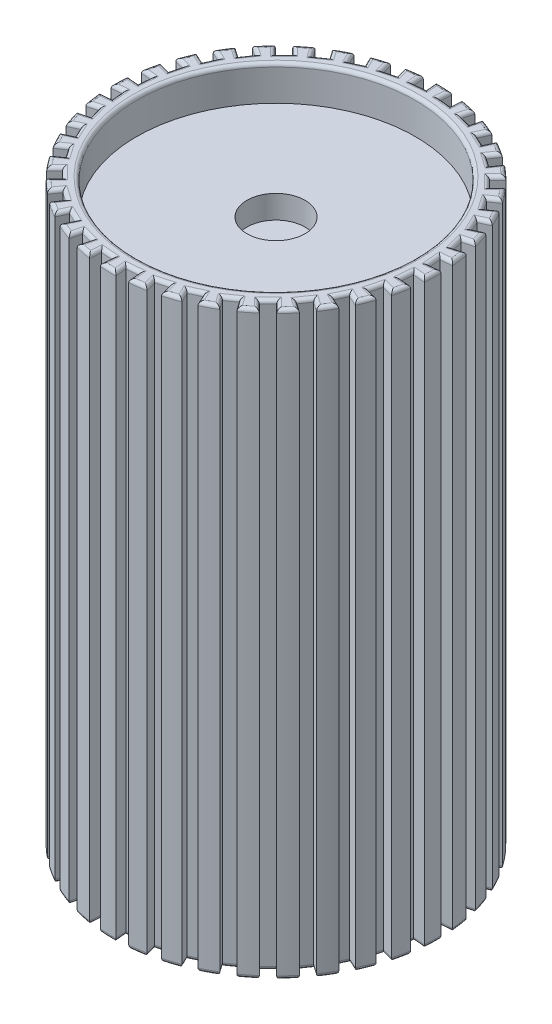
SolidWorks part; units mm, degrees
ref_plane "Front Plane" through (0, 0, 0) normal (0, 0, 1) x (1, 0, 0)
ref_plane "Top Plane" through (0, 0, 0) normal (0, 1, 0) x (1, 0, 0)
ref_plane "Right Plane" through (0, 0, 0) normal (1, 0, 0) x (0, 0, -1)
other "Configuration Table"
sketch "草图1" plane through (0, 0, 0) normal (0, 1, 0) x (1, 0, 0)
  circle A0 centre (0, 0) radius 13
  dimension "D1" = 26
extrude "凸台-拉伸1" add sketch "草图1" along normal blind 50
sketch "草图6" plane through (0, 50, 0) normal (0, 1, 0) x (1, 0, 0)
  circle A0 centre (0, 0) radius 14
  dimension "D1" = 28
extrude "凸台-拉伸4" add sketch "草图6" against normal through all
sketch "草图2" plane through (0, 50, 0) normal (0, 1, 0) x (1, 0, 0)
  circle A0 centre (0, 0) radius 12
  dimension "D1" = 24
extrude "切除-拉伸1" cut sketch "草图2" against normal blind 3
sketch "草图7" plane through (0, 50, 0) normal (0, 1, 0) x (1, 0, 0)
  line L0 (-15.6468, 4.1422) -> (-12.5671, 3.3269)
  line L1 (-15.6468, 4.1422) -> (-15.3762, 5.1646)
  line L2 (-12.5671, 3.3269) -> (-12.2964, 4.3493)
  line L3 (-15.3762, 5.1646) -> (-12.2964, 4.3493)
  line L4 (-14.6898, 6.7963) -> (-11.7985, 5.4586)
  line L5 (-14.6898, 6.7963) -> (-14.2457, 7.7562)
  line L6 (-14.2457, 7.7562) -> (-11.3544, 6.4185)
  line L7 (-11.7985, 5.4586) -> (-11.3544, 6.4185)
  line L8 (-13.2865, 9.2439) -> (-10.6713, 7.4245)
  line L9 (-13.2865, 9.2439) -> (-12.6825, 10.1121)
  line L10 (-12.6825, 10.1121) -> (-10.0673, 8.2926)
  line L11 (-10.6713, 7.4245) -> (-10.0673, 8.2926)
  line L12 (-11.4794, 11.4107) -> (-9.22, 9.1647)
  line L13 (-11.4794, 11.4107) -> (-10.7338, 12.1608)
  line L14 (-10.7338, 12.1608) -> (-8.4744, 9.9148)
  line L15 (-9.22, 9.1647) -> (-8.4744, 9.9148)
  line L16 (-9.3236, 13.2307) -> (-7.4884, 10.6265)
  line L17 (-9.3236, 13.2307) -> (-8.4591, 13.8399)
  line L18 (-8.4591, 13.8399) -> (-6.6239, 11.2358)
  line L19 (-7.4884, 10.6265) -> (-6.6239, 11.2358)
  line L20 (-6.8845, 14.6487) -> (-5.5294, 11.7654)
  line L21 (-6.8845, 14.6487) -> (-5.9273, 15.0986)
  line L22 (-5.9273, 15.0986) -> (-4.5722, 12.2153)
  line L23 (-5.5294, 11.7654) -> (-4.5722, 12.2153)
  line L24 (-4.2361, 15.6217) -> (-3.4024, 12.5469)
  line L25 (-4.2361, 15.6217) -> (-3.2154, 15.8985)
  line L26 (-3.2154, 15.8985) -> (-2.3816, 12.8237)
  line L27 (-3.4024, 12.5469) -> (-2.3816, 12.8237)
  line L28 (-1.4591, 16.1199) -> (-1.1719, 12.9471)
  line L29 (-1.4591, 16.1199) -> (-0.4058, 16.2153)
  line L30 (-0.4058, 16.2153) -> (-0.1186, 13.0424)
  line L31 (-1.1719, 12.9471) -> (-0.1186, 13.0424)
  line L32 (1.3622, 16.1284) -> (1.0941, 12.9539)
  line L33 (1.3622, 16.1284) -> (2.4161, 16.0394)
  line L34 (2.4161, 16.0394) -> (2.148, 12.8649)
  line L35 (1.0941, 12.9539) -> (2.148, 12.8649)
  line L36 (4.1422, 15.6468) -> (3.3269, 12.5671)
  line L37 (4.1422, 15.6468) -> (5.1646, 15.3762)
  line L38 (5.1646, 15.3762) -> (4.3493, 12.2964)
  line L39 (3.3269, 12.5671) -> (4.3493, 12.2964)
  line L40 (6.7963, 14.6898) -> (5.4586, 11.7985)
  line L41 (6.7963, 14.6898) -> (7.7562, 14.2457)
  line L42 (7.7562, 14.2457) -> (6.4185, 11.3544)
  line L43 (5.4586, 11.7985) -> (6.4185, 11.3544)
  line L44 (9.2439, 13.2865) -> (7.4245, 10.6713)
  line L45 (9.2439, 13.2865) -> (10.1121, 12.6825)
  line L46 (10.1121, 12.6825) -> (8.2926, 10.0673)
  line L47 (7.4245, 10.6713) -> (8.2926, 10.0673)
  line L48 (11.4107, 11.4794) -> (9.1647, 9.22)
  line L49 (11.4107, 11.4794) -> (12.1608, 10.7338)
  line L50 (12.1608, 10.7338) -> (9.9148, 8.4744)
  line L51 (9.1647, 9.22) -> (9.9148, 8.4744)
  line L52 (13.2307, 9.3236) -> (10.6265, 7.4884)
  line L53 (13.2307, 9.3236) -> (13.8399, 8.4591)
  line L54 (13.8399, 8.4591) -> (11.2358, 6.6239)
  line L55 (10.6265, 7.4884) -> (11.2358, 6.6239)
  line L56 (14.6487, 6.8845) -> (11.7654, 5.5294)
  line L57 (14.6487, 6.8845) -> (15.0986, 5.9273)
  line L58 (15.0986, 5.9273) -> (12.2153, 4.5722)
  line L59 (11.7654, 5.5294) -> (12.2153, 4.5722)
  line L60 (15.6217, 4.2361) -> (12.5469, 3.4024)
  line L61 (15.6217, 4.2361) -> (15.8985, 3.2154)
  line L62 (15.8985, 3.2154) -> (12.8237, 2.3816)
  line L63 (12.5469, 3.4024) -> (12.8237, 2.3816)
  line L64 (16.1199, 1.4591) -> (12.9471, 1.1719)
  line L65 (16.1199, 1.4591) -> (16.2153, 0.4058)
  line L66 (16.2153, 0.4058) -> (13.0424, 0.1186)
  line L67 (12.9471, 1.1719) -> (13.0424, 0.1186)
  line L68 (16.1284, -1.3622) -> (12.9539, -1.0941)
  line L69 (16.1284, -1.3622) -> (16.0394, -2.4161)
  line L70 (16.0394, -2.4161) -> (12.8649, -2.148)
  line L71 (12.9539, -1.0941) -> (12.8649, -2.148)
  line L72 (15.6468, -4.1422) -> (12.5671, -3.3269)
  line L73 (15.6468, -4.1422) -> (15.3762, -5.1646)
  line L74 (15.3762, -5.1646) -> (12.2964, -4.3493)
  line L75 (12.5671, -3.3269) -> (12.2964, -4.3493)
  line L76 (14.6898, -6.7963) -> (11.7985, -5.4586)
  line L77 (14.6898, -6.7963) -> (14.2457, -7.7562)
  line L78 (14.2457, -7.7562) -> (11.3544, -6.4185)
  line L79 (11.7985, -5.4586) -> (11.3544, -6.4185)
  line L80 (13.2865, -9.2439) -> (10.6713, -7.4245)
  line L81 (13.2865, -9.2439) -> (12.6825, -10.1121)
  line L82 (12.6825, -10.1121) -> (10.0673, -8.2926)
  line L83 (10.6713, -7.4245) -> (10.0673, -8.2926)
  line L84 (11.4794, -11.4107) -> (9.22, -9.1647)
  line L85 (11.4794, -11.4107) -> (10.7338, -12.1608)
  line L86 (10.7338, -12.1608) -> (8.4744, -9.9148)
  line L87 (9.22, -9.1647) -> (8.4744, -9.9148)
  line L88 (9.3236, -13.2307) -> (7.4884, -10.6265)
  line L89 (9.3236, -13.2307) -> (8.4591, -13.8399)
  line L90 (8.4591, -13.8399) -> (6.6239, -11.2358)
  line L91 (7.4884, -10.6265) -> (6.6239, -11.2358)
  line L92 (6.8845, -14.6487) -> (5.5294, -11.7654)
  line L93 (6.8845, -14.6487) -> (5.9273, -15.0986)
  line L94 (5.9273, -15.0986) -> (4.5722, -12.2153)
  line L95 (5.5294, -11.7654) -> (4.5722, -12.2153)
  line L96 (4.2361, -15.6217) -> (3.4024, -12.5469)
  line L97 (4.2361, -15.6217) -> (3.2154, -15.8985)
  line L98 (3.2154, -15.8985) -> (2.3816, -12.8237)
  line L99 (3.4024, -12.5469) -> (2.3816, -12.8237)
  line L100 (1.4591, -16.1199) -> (1.1719, -12.9471)
  line L101 (1.4591, -16.1199) -> (0.4058, -16.2153)
  line L102 (0.4058, -16.2153) -> (0.1186, -13.0424)
  line L103 (1.1719, -12.9471) -> (0.1186, -13.0424)
  line L104 (-1.3622, -16.1284) -> (-1.0941, -12.9539)
  line L105 (-1.3622, -16.1284) -> (-2.4161, -16.0394)
  line L106 (-2.4161, -16.0394) -> (-2.148, -12.8649)
  line L107 (-1.0941, -12.9539) -> (-2.148, -12.8649)
  line L108 (-4.1422, -15.6468) -> (-3.3269, -12.5671)
  line L109 (-4.1422, -15.6468) -> (-5.1646, -15.3762)
  line L110 (-5.1646, -15.3762) -> (-4.3493, -12.2964)
  line L111 (-3.3269, -12.5671) -> (-4.3493, -12.2964)
  line L112 (-6.7963, -14.6898) -> (-5.4586, -11.7985)
  line L113 (-6.7963, -14.6898) -> (-7.7562, -14.2457)
  line L114 (-7.7562, -14.2457) -> (-6.4185, -11.3544)
  line L115 (-5.4586, -11.7985) -> (-6.4185, -11.3544)
  line L116 (-9.2439, -13.2865) -> (-7.4245, -10.6713)
  line L117 (-9.2439, -13.2865) -> (-10.1121, -12.6825)
  line L118 (-10.1121, -12.6825) -> (-8.2926, -10.0673)
  line L119 (-7.4245, -10.6713) -> (-8.2926, -10.0673)
  line L120 (-11.4107, -11.4794) -> (-9.1647, -9.22)
  line L121 (-11.4107, -11.4794) -> (-12.1608, -10.7338)
  line L122 (-12.1608, -10.7338) -> (-9.9148, -8.4744)
  line L123 (-9.1647, -9.22) -> (-9.9148, -8.4744)
  line L124 (-13.2307, -9.3236) -> (-10.6265, -7.4884)
  line L125 (-13.2307, -9.3236) -> (-13.8399, -8.4591)
  line L126 (-13.8399, -8.4591) -> (-11.2358, -6.6239)
  line L127 (-10.6265, -7.4884) -> (-11.2358, -6.6239)
  line L128 (-14.6487, -6.8845) -> (-11.7654, -5.5294)
  line L129 (-14.6487, -6.8845) -> (-15.0986, -5.9273)
  line L130 (-15.0986, -5.9273) -> (-12.2153, -4.5722)
  line L131 (-11.7654, -5.5294) -> (-12.2153, -4.5722)
  line L132 (-15.6217, -4.2361) -> (-12.5469, -3.4024)
  line L133 (-15.6217, -4.2361) -> (-15.8985, -3.2154)
  line L134 (-15.8985, -3.2154) -> (-12.8237, -2.3816)
  line L135 (-12.5469, -3.4024) -> (-12.8237, -2.3816)
  line L136 (-16.1199, -1.4591) -> (-12.9471, -1.1719)
  line L137 (-16.1199, -1.4591) -> (-16.2153, -0.4058)
  line L138 (-16.2153, -0.4058) -> (-13.0424, -0.1186)
  line L139 (-12.9471, -1.1719) -> (-13.0424, -0.1186)
  line L140 (-16.1284, 1.3622) -> (-12.9539, 1.0941)
  line L141 (-16.1284, 1.3622) -> (-16.0394, 2.4161)
  line L142 (-16.0394, 2.4161) -> (-12.8649, 2.148)
  line L143 (-12.9539, 1.0941) -> (-12.8649, 2.148)
  circle A0 centre (0, 0) radius 13 construction
  point P150 (0, 0)
  dimension "D1" = 26
  dimension "D2" = 36
extrude "切除-拉伸2" cut sketch "草图7" against normal through all
sketch "草图8" plane through (0, 47, 0) normal (0, 1, 0) x (1, 0, 0)
  circle A0 centre (0, 0) radius 2.5
  dimension "D1" = 5
extrude "切除-拉伸3" cut sketch "草图8" against normal blind 2
fillet "圆角6" radius 0.3 144 edges at (1.1362, 0, -13.4521) (0.4872, 0, -13.9915) (-0.1619, 0, -13.5205) (-0.6453, 0, -12.9947) (-1.217, 0, -13.445) (-1.9498, 0, -13.8636) (-2.5072, 0, -13.2869) (-2.892, 0, -12.6853) (-3.5332, 0, -13.0294) (-4.3276, 0, -13.3143) (-4.7764, 0, -12.6497) (-5.0508, 0, -11.9904) (-5.7421, 0, -12.218) (-6.5739, 0, -12.3606) (-6.9004, 0, -11.6281) (-7.0562, 0, -10.9311) (-7.7765, 0, -11.0352) (-8.6204, 0, -11.0313) (-8.8148, 0, -10.2532) (-8.8472, 0, -9.5398) (-9.5746, 0, -9.5172) (-10.405, 0, -9.3668) (-10.4613, 0, -8.5668) (-10.3693, 0, -7.8586) (-11.0818, 0, -7.71) (-11.8734, 0, -7.4177) (-11.79, 0, -6.62) (-11.5764, 0, -5.9386) (-12.2522, 0, -5.6686) (-12.9811, 0, -5.2432) (-12.7604, 0, -4.4722) (-12.4318, 0, -3.8381) (-13.0504, 0, -3.4549) (-13.6944, 0, -2.9094) (-13.3432, 0, -2.1884) (-12.9094, 0, -1.6211) (-13.4521, 0, -1.1362) (-13.9915, 0, -0.4872) (-13.5205, 0, 0.1619) (-12.9947, 0, 0.6453) (-13.445, 0, 1.217) (-13.8636, 0, 1.9498) (-13.2869, 0, 2.5072) (-12.6853, 0, 2.892) (-13.0294, 0, 3.5332) (-13.3143, 0, 4.3276) (-12.6497, 0, 4.7764) (-11.9904, 0, 5.0508) (-12.218, 0, 5.7421) (-12.3606, 0, 6.5739) (-11.6281, 0, 6.9004) (-10.9311, 0, 7.0562) (-11.0352, 0, 7.7765) (-11.0313, 0, 8.6204) (-10.2532, 0, 8.8148) (-9.5398, 0, 8.8472) (-9.5172, 0, 9.5746) (-9.3668, 0, 10.405) (-8.5668, 0, 10.4613) (-7.8586, 0, 10.3693) (-7.71, 0, 11.0818) (-7.4177, 0, 11.8734) (-6.62, 0, 11.79) (-5.9386, 0, 11.5764) (-5.6686, 0, 12.2522) (-5.2432, 0, 12.9811) (-4.4722, 0, 12.7604) (-3.8381, 0, 12.4318) (-3.4549, 0, 13.0504) (-2.9094, 0, 13.6944) (-2.1884, 0, 13.3432) (-1.6211, 0, 12.9094) (-1.1362, 0, 13.4521) (-0.4872, 0, 13.9915) (0.1619, 0, 13.5205) (0.6453, 0, 12.9947) (1.217, 0, 13.445) (1.9498, 0, 13.8636) (2.5072, 0, 13.2869) (2.892, 0, 12.6853) (3.5332, 0, 13.0294) (4.3276, 0, 13.3143) (4.7764, 0, 12.6497) (5.0508, 0, 11.9904) (5.7421, 0, 12.218) (6.5739, 0, 12.3606) (6.9004, 0, 11.6281) (7.0562, 0, 10.9311) (7.7765, 0, 11.0352) (8.6204, 0, 11.0313) (8.8148, 0, 10.2532) (8.8472, 0, 9.5398) (9.5746, 0, 9.5172) (10.405, 0, 9.3668) (10.4613, 0, 8.5668) (10.3693, 0, 7.8586) (11.0818, 0, 7.71) (11.8734, 0, 7.4177) (11.79, 0, 6.62) (11.5764, 0, 5.9386) (12.2522, 0, 5.6686) (12.9811, 0, 5.2432) (12.7604, 0, 4.4722) (12.4318, 0, 3.8381) (13.0504, 0, 3.4549) (13.6944, 0, 2.9094) (13.3432, 0, 2.1884) (12.9094, 0, 1.6211) (13.4521, 0, 1.1362) (13.9915, 0, 0.4872) (13.5205, 0, -0.1619) (12.9947, 0, -0.6453) (13.445, 0, -1.217) (13.8636, 0, -1.9498) (13.2869, 0, -2.5072) (12.6853, 0, -2.892) (13.0294, 0, -3.5332) (13.3143, 0, -4.3276) (12.6497, 0, -4.7764) (11.9904, 0, -5.0508) (12.218, 0, -5.7421) (12.3606, 0, -6.5739) (11.6281, 0, -6.9004) (10.9311, 0, -7.0562) (11.0352, 0, -7.7765) (11.0313, 0, -8.6204) (10.2532, 0, -8.8148) (9.5398, 0, -8.8472) (9.5172, 0, -9.5746) (9.3668, 0, -10.405) (8.5668, 0, -10.4613) (7.8586, 0, -10.3693) (7.71, 0, -11.0818) (7.4177, 0, -11.8734) (6.62, 0, -11.79) (5.9386, 0, -11.5764) (5.6686, 0, -12.2522) (5.2432, 0, -12.9811) (4.4722, 0, -12.7604) (3.8381, 0, -12.4318) (3.4549, 0, -13.0504) (2.9094, 0, -13.6944) (2.1884, 0, -13.3432) (1.6211, 0, -12.9094)
fillet "圆角7" radius 0.3 145 edges at (0, 50, 12) (2.9094, 50, -13.6944) (3.4549, 50, -13.0504) (3.8381, 50, -12.4318) (4.4722, 50, -12.7604) (5.2432, 50, -12.9811) (5.6686, 50, -12.2522) (5.9386, 50, -11.5764) (6.62, 50, -11.79) (7.4177, 50, -11.8734) (7.71, 50, -11.0818) (7.8586, 50, -10.3693) (8.5668, 50, -10.4613) (9.3668, 50, -10.405) (9.5172, 50, -9.5746) (9.5398, 50, -8.8472) (10.2532, 50, -8.8148) (11.0313, 50, -8.6204) (11.0352, 50, -7.7765) (10.9311, 50, -7.0562) (11.6281, 50, -6.9004) (12.3606, 50, -6.5739) (12.218, 50, -5.7421) (11.9904, 50, -5.0508) (12.6497, 50, -4.7764) (13.3143, 50, -4.3276) (13.0294, 50, -3.5332) (12.6853, 50, -2.892) (13.2869, 50, -2.5072) (13.8636, 50, -1.9498) (13.445, 50, -1.217) (12.9947, 50, -0.6453) (13.5205, 50, -0.1619) (13.9915, 50, 0.4872) (13.4521, 50, 1.1362) (12.9094, 50, 1.6211) (13.3432, 50, 2.1884) (13.6944, 50, 2.9094) (13.0504, 50, 3.4549) (12.4318, 50, 3.8381) (12.7604, 50, 4.4722) (12.9811, 50, 5.2432) (12.2522, 50, 5.6686) (11.5764, 50, 5.9386) (11.79, 50, 6.62) (11.8734, 50, 7.4177) (11.0818, 50, 7.71) (10.3693, 50, 7.8586) (10.4613, 50, 8.5668) (10.405, 50, 9.3668) (9.5746, 50, 9.5172) (8.8472, 50, 9.5398) (8.8148, 50, 10.2532) (8.6204, 50, 11.0313) (7.7765, 50, 11.0352) (7.0562, 50, 10.9311) (6.9004, 50, 11.6281) (6.5739, 50, 12.3606) (5.7421, 50, 12.218) (5.0508, 50, 11.9904) (4.7764, 50, 12.6497) (4.3276, 50, 13.3143) (3.5332, 50, 13.0294) (2.892, 50, 12.6853) (2.5072, 50, 13.2869) (1.9498, 50, 13.8636) (1.217, 50, 13.445) (0.6453, 50, 12.9947) (0.1619, 50, 13.5205) (-0.4872, 50, 13.9915) (-1.1362, 50, 13.4521) (-1.6211, 50, 12.9094) (-2.1884, 50, 13.3432) (-2.9094, 50, 13.6944) (-3.4549, 50, 13.0504) (-3.8381, 50, 12.4318) (-4.4722, 50, 12.7604) (-5.2432, 50, 12.9811) (-5.6686, 50, 12.2522) (-5.9386, 50, 11.5764) (-6.62, 50, 11.79) (-7.4177, 50, 11.8734) (-7.71, 50, 11.0818) (-7.8586, 50, 10.3693) (-8.5668, 50, 10.4613) (-9.3668, 50, 10.405) (-9.5172, 50, 9.5746) (-9.5398, 50, 8.8472) (-10.2532, 50, 8.8148) (-11.0313, 50, 8.6204) (-11.0352, 50, 7.7765) (-10.9311, 50, 7.0562) (-11.6281, 50, 6.9004) (-12.3606, 50, 6.5739) (-12.218, 50, 5.7421) (-11.9904, 50, 5.0508) (-12.6497, 50, 4.7764) (-13.3143, 50, 4.3276) (-13.0294, 50, 3.5332) (-12.6853, 50, 2.892) (-13.2869, 50, 2.5072) (-13.8636, 50, 1.9498) (-13.445, 50, 1.217) (-12.9947, 50, 0.6453) (-13.5205, 50, 0.1619) (-13.9915, 50, -0.4872) (-13.4521, 50, -1.1362) (-12.9094, 50, -1.6211) (-13.3432, 50, -2.1884) (-13.6944, 50, -2.9094) (-13.0504, 50, -3.4549) (-12.4318, 50, -3.8381) (-12.7604, 50, -4.4722) (-12.9811, 50, -5.2432) (-12.2522, 50, -5.6686) (-11.5764, 50, -5.9386) (-11.79, 50, -6.62) (-11.8734, 50, -7.4177) (-11.0818, 50, -7.71) (-10.3693, 50, -7.8586) (-10.4613, 50, -8.5668) (-10.405, 50, -9.3668) (-9.5746, 50, -9.5172) (-8.8472, 50, -9.5398) (-8.8148, 50, -10.2532) (-8.6204, 50, -11.0313) (-7.7765, 50, -11.0352) (-7.0562, 50, -10.9311) (-6.9004, 50, -11.6281) (-6.5739, 50, -12.3606) (-5.7421, 50, -12.218) (-5.0508, 50, -11.9904) (-4.7764, 50, -12.6497) (-4.3276, 50, -13.3143) (-3.5332, 50, -13.0294) (-2.892, 50, -12.6853) (-2.5072, 50, -13.2869) (-1.9498, 50, -13.8636) (-1.217, 50, -13.445) (-0.6453, 50, -12.9947) (-0.1619, 50, -13.5205) (0.4872, 50, -13.9915) (1.1362, 50, -13.4521) (1.6211, 50, -12.9094) (2.1884, 50, -13.3432)
